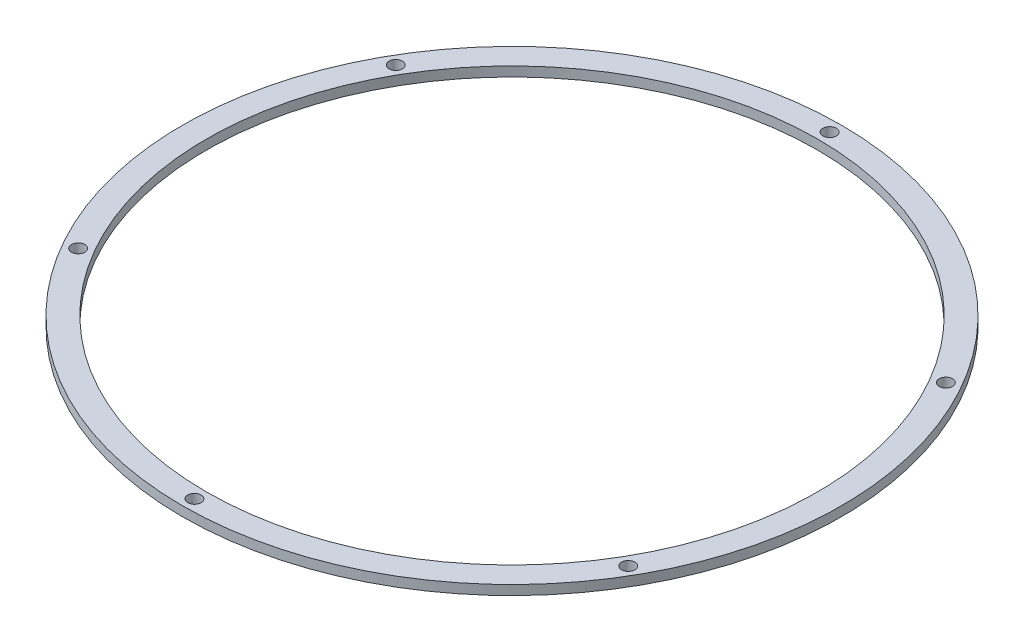
SolidWorks part; units mm, degrees
ref_plane "Front Plane" through (0, 0, 0) normal (0, 0, 1) x (1, 0, 0)
ref_plane "Top Plane" through (0, 0, 0) normal (0, 1, 0) x (1, 0, 0)
ref_plane "Right Plane" through (0, 0, 0) normal (1, 0, 0) x (0, 0, -1)
sketch "Sketch1" plane through (0, 0, 0) normal (0, 1, 0) x (1, 0, 0)
  line L0 (0, 168.5) -> (0, 0) construction
  line L1 (0, 174.85) -> (0, 162.15) construction
  line L2 (0, -55) -> (0, 55) construction
  circle A0 centre (0, 0) radius 168.5 construction
  circle A1 centre (0, 168.5) radius 3.556
  circle A2 centre (145.9253, 84.25) radius 3.556
  circle A3 centre (145.9253, -84.25) radius 3.556
  circle A4 centre (0, -168.5) radius 3.556
  circle A5 centre (-145.9253, -84.25) radius 3.556
  circle A6 centre (-145.9253, 84.25) radius 3.556
  circle A7 centre (0, 0) radius 174.85
  circle A8 centre (0, 0) radius 162.15
  point P17 (0, 0)
  point P20 (0, 168.5)
  dimension "D1" = 7.112
  dimension "D2" = 337
  dimension "D6" = 12.7
  dimension "D4" = 60
  dimension "D5" = 60
  dimension "D3" = 6
extrude "Boss-Extrude1" add sketch "Sketch1" along normal blind 5.08
